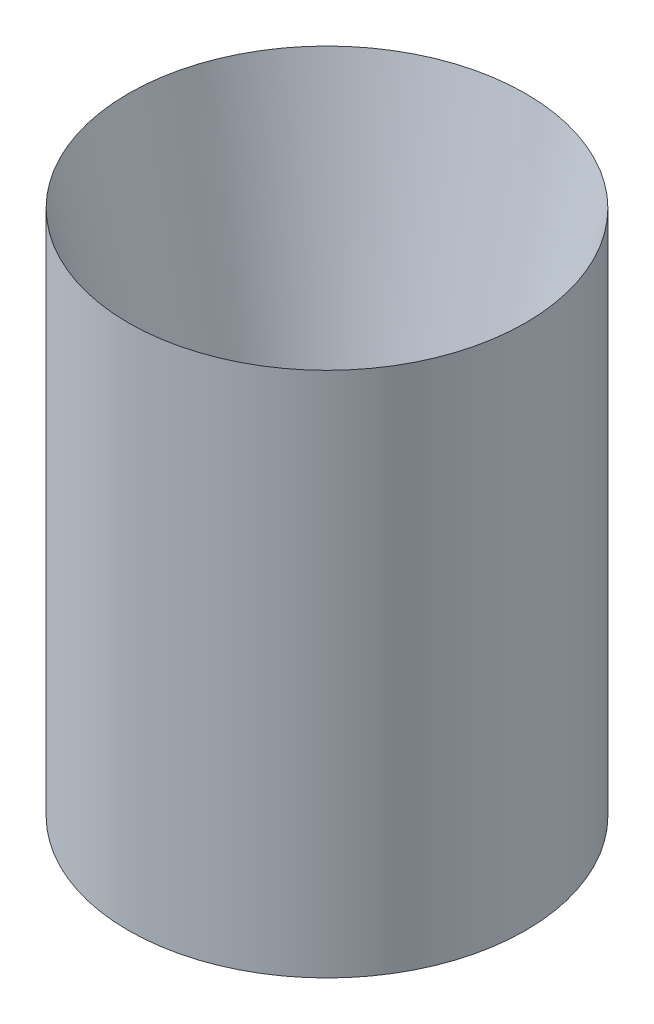
SolidWorks part; units mm, degrees
ref_plane "Front Plane" through (0, 0, 0) normal (1, 0, 0) x (0, 1, 0)
ref_plane "Top Plane" through (0, 0, 0) normal (0, 0, 1) x (0, 1, 0)
ref_plane "Right Plane" through (0, 0, 0) normal (0, 1, 0) x (-1, 0, 0)
sketch "Sketch1" plane through (0, 0, 0) normal (0, 0, 1) x (0, 1, 0)
  line L0 (0, 22.225) -> (0, 53.975)
  line L1 (0, 53.975) -> (143.002, 53.975)
  line L2 (143.002, 53.975) -> (0, 22.225)
  line L3 (0, 0) -> (143.002, 0) construction
  point P0 (0, 22.225)
  dimension "D1" = 22.225
  dimension "D2" = 53.975
  dimension "D3" = 143.002
revolve "Revolve1" add sketch "Sketch1" angle 360 about L3
